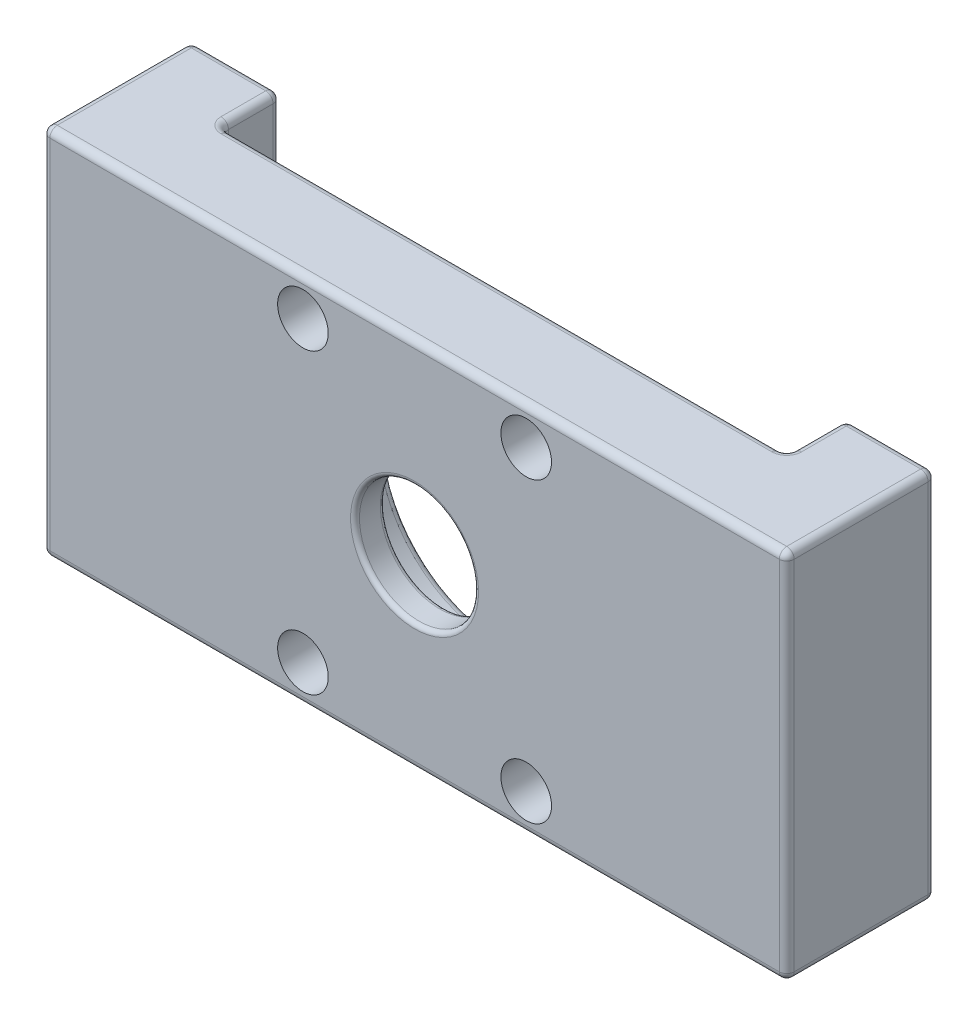
SolidWorks part; units mm, degrees
ref_plane "Front Plane" through (0, 0, 0) normal (0, 0, 1) x (1, 0, 0)
ref_plane "Top Plane" through (0, 0, 0) normal (0, 1, 0) x (1, 0, 0)
ref_plane "Right Plane" through (0, 0, 0) normal (1, 0, 0) x (0, 0, -1)
sketch "Sketch1" plane through (0, 0, 0) normal (0, 0, 1) x (1, 0, 0)
  line L0 (17.35, 12.5) -> (17.35, 10) construction
  line L1 (-7.65, 0) -> (-5.1989, 0) construction
  line L8 (-7.65, 12.5) -> (-7.65, -12.5)
  line L9 (-7.65, -12.5) -> (42.35, -12.5)
  line L10 (42.35, -12.5) -> (42.35, 12.5)
  line L11 (42.35, 12.5) -> (-7.65, 12.5)
  circle A1 centre (9.85, 10) radius 1.7
  circle A2 centre (24.85, 10) radius 1.7
  circle A3 centre (24.85, -10) radius 1.7
  circle A4 centre (9.85, -10) radius 1.7
  dimension "D2" = 3.4
  dimension "D1" = 25
  dimension "D3" = 25
extrude "Boss-Extrude1" add sketch "Sketch1" along normal blind 6
sketch "Sketch2" plane through (0, 0, 6) normal (0, 0, 1) x (1, 0, 0)
  circle A0 centre (17.35, 0) radius 4
  dimension "D1" = 8
extrude "Cut-Extrude1" cut sketch "Sketch2" against normal blind 4
sketch "Sketch3" plane through (0, 0, 2) normal (0, 0, 1) x (1, 0, 0)
  circle A0 centre (17.35, 0) radius 7.9
  dimension "D1" = 15.8
extrude "Cut-Extrude2" cut sketch "Sketch3" against normal through all and the other way blind 2
sketch "Sketch5" plane through (0, 0, 0) normal (0, 0, -1) x (-1, 0, 0)
  line L0 (7.65, -12.5) -> (-42.35, -12.5) construction
  line L1 (7.65, 12.5) -> (1.65, 12.5)
  line L2 (7.65, 12.5) -> (7.65, -12.5)
  line L3 (7.65, -12.5) -> (1.65, -12.5)
  line L4 (1.65, 12.5) -> (1.65, -12.5)
  line L5 (-17.35, 12.5) -> (-17.35, 15.3119) construction
  line L7 (-36.35, 12.5) -> (-36.35, -12.5)
  line L8 (-42.35, -12.5) -> (-36.35, -12.5)
  line L9 (-42.35, 12.5) -> (-42.35, -12.5)
  line L10 (-42.35, 12.5) -> (-36.35, 12.5)
  dimension "D1" = 6
extrude "Boss-Extrude3" add sketch "Sketch5" along normal blind 4
fillet "Fillet1" radius 0.5 26 edges at (-7.65, 12.5, 1) (-7.65, -12.5, 1) (42.35, -12.5, 1) (42.35, 12.5, 1) (42.35, 0, 6) (17.35, -12.5, 6) (-7.65, 0, 6) (17.35, 12.5, 6) (17.35, -12.5, 0) (17.35, 12.5, 0) (11.55, 10, 0) (23.15, 10, 0) (-1.65, 12.5, -2) (-1.65, -12.5, -2) (-4.65, -12.5, -4) (-1.65, 0, -4) (-4.65, 12.5, -4) (-7.65, 0, -4) (-1.65, 0, 0) (36.35, 0, 0) (39.35, 12.5, -4) (42.35, 0, -4) (39.35, -12.5, -4) (36.35, 0, -4) (36.35, 12.5, -2) (36.35, -12.5, -2)
fillet "Fillet2" radius 0.5 1 edges at (25.25, 0, 0)
fillet "Fillet3" radius 0.3 2 edges at (21.35, 0, 6) (21.35, 0, 4)
